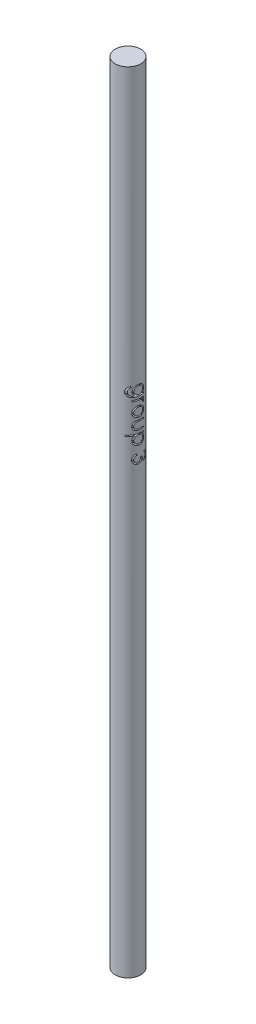
SolidWorks part; units mm, degrees
ref_plane "Front Plane" through (0, 0, 0) normal (0, 0, 1) x (1, 0, 0)
ref_plane "Top Plane" through (0, 0, 0) normal (0, 1, 0) x (1, 0, 0)
ref_plane "Right Plane" through (0, 0, 0) normal (1, 0, 0) x (0, 0, -1)
sketch "Sketch1" plane through (0, 0, 0) normal (0, 1, 0) x (1, 0, 0)
  circle A0 centre (0, 0) radius 1
  dimension "D1" = 2
extrude "Boss-Extrude1" add sketch "Sketch1" along normal blind 61.8
ref_plane "Plane1" through (1, 0, 0) normal (1, 0, 0) x (0, 0, -1)
sketch "Sketch2" plane through (1, 0, 0) normal (1, 0, 0) x (0, 0, -1)
  line L0 (-0.5313, 40.2168) -> (-0.5313, 25.4826) construction
  text T0 "group 3" font "Century Gothic" height in points 4
  point P2 (0, 51.4137)
  point P3 (0, 34.0528)
  point P5 (0, 50.3987)
  point P6 (0, 47.8345)
  point P8 (0, 61.8)
  point P9 (0, 40.2168)
  point P10 (0, 25.4826)
extrude "Cut-Extrude1" cut sketch "Sketch2" against normal blind 1
